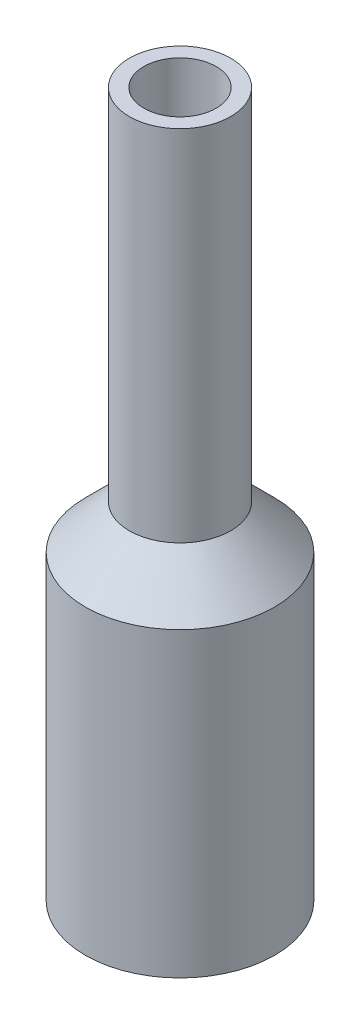
SolidWorks part; units mm, degrees
ref_plane "Front Plane" through (0, 0, 0) normal (0, 0, 1) x (1, 0, 0)
ref_plane "Top Plane" through (0, 0, 0) normal (0, 1, 0) x (1, 0, 0)
ref_plane "Right Plane" through (0, 0, 0) normal (1, 0, 0) x (0, 0, -1)
sketch "Sketch1" plane through (0, 0, 0) normal (0, 0, 1) x (1, 0, 0)
  line L0 (0, 19.759) -> (0, -8.4218) construction
  point P3 (0, 19.759)
  point P4 (0, -8.4218)
sketch "Sketch2" plane through (0, 0, 0) normal (0, 0, 1) x (1, 0, 0)
  line L0 (0, 19.759) -> (0, -8.4218) construction
  line L1 (0.75, 10.6766) -> (1.05, 10.6766)
  line L2 (0.75, 10.6766) -> (0.75, 2.6766)
  line L3 (0.75, 2.6766) -> (1.05, 2.6766)
  line L4 (1.05, 10.6766) -> (1.05, 2.6766)
  dimension "D1" = 0.3
  dimension "D2" = 8
  dimension "D3" = 0.75
sketch "Sketch3" plane through (0, 0, 0) normal (0, 0, 1) x (1, 0, 0)
  line L0 (0.75, 2.6766) -> (1.05, 2.6766) construction
  line L2 (0.9, 2.6766) -> (1.05, 2.6766)
  line L3 (1.05, 2.6766) -> (1.05, 3.2406)
  line L4 (1.05, 3.2406) -> (1.962, 2.3287)
  line L5 (1.962, 2.3287) -> (1.962, -3.9234)
  line L6 (0.9, 2.6766) -> (1.8381, 2.3287)
  line L7 (1.8381, 2.3287) -> (1.8381, -3.9234)
  line L8 (1.8381, -3.9234) -> (1.962, -3.9234)
  line L9 (0.75, 10.6766) -> (1.05, 10.6766) construction
  line L10 (1.05, 3.2406) -> (1.05, 10.6766) construction
  dimension "D1" = 14.6
revolve "Revolve1" add sketch "Sketch3" angle 360 about L0
revolve "Revolve2" add sketch "Sketch2" angle 360 about L0
sketch "Sketch4" plane through (0, 2.6766, 0) normal (0, -1, 0) x (1, 0, 0)
  point P0 (0, 0)
other "CPoint1" parameters "Diameter"=2, "StubLength"=2
ref_axis "Axis1" through (0, -7.3234, 0) along (0, 1, 0)
